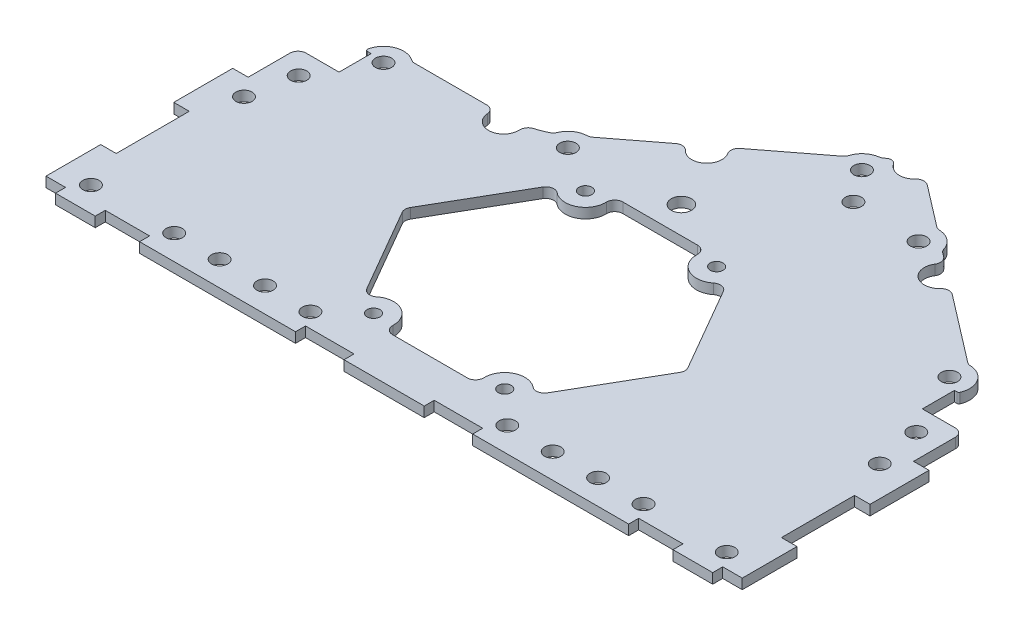
SolidWorks part; units mm, degrees
material "Alum Plate"
ref_plane "Front Plane" through (0, 0, 0) normal (0, 0, 1) x (1, 0, 0)
ref_plane "Top Plane" through (0, 0, 0) normal (0, 1, 0) x (1, 0, 0)
ref_plane "Right Plane" through (0, 0, 0) normal (1, 0, 0) x (0, 0, -1)
sketch "Top Layout" plane through (0, 0, 0) normal (0, 1, 0) x (1, 0, 0)
  line L0 (-114.046, -123.825) -> (-104.775, -123.825) construction
  line L1 (-104.775, -142.875) -> (-101.6, -142.875)
  line L2 (-104.775, -142.875) -> (-104.775, -104.775)
  line L3 (-104.775, -104.775) -> (-101.6, -104.775)
  line L4 (-101.6, -142.875) -> (-101.6, -104.775)
  line L5 (-104.775, -142.875) -> (-101.6, -104.775) construction
  line L6 (-104.775, -104.775) -> (-101.6, -142.875) construction
  line L7 (-19.05, -105.8164) -> (-101.6, -105.8164)
  line L8 (-19.05, -105.8164) -> (-19.05, -141.8336)
  line L9 (-19.05, -141.8336) -> (-101.6, -141.8336)
  line L10 (-101.6, -105.8164) -> (-101.6, -141.8336)
  line L11 (-19.05, -105.8164) -> (-101.6, -141.8336) construction
  line L12 (-19.05, -141.8336) -> (-101.6, -105.8164) construction
  line L13 (-133.096, -85.725) -> (-114.046, -85.725)
  line L14 (-133.096, -85.725) -> (-133.096, -161.925)
  line L15 (-133.096, -161.925) -> (-114.046, -161.925)
  line L16 (-114.046, -85.725) -> (-114.046, -161.925)
  line L17 (-133.096, -85.725) -> (-114.046, -161.925) construction
  line L18 (-133.096, -161.925) -> (-114.046, -85.725) construction
  line L19 (-104.775, -123.825) -> (0, -123.825) construction
  line L20 (0, -123.825) -> (0, 0) construction
  line L21 (-52.3528, -40.1717) -> (0, 0) construction
  line L22 (-70.6449, -16.3328) -> (-18.2922, 23.8388)
  line L23 (-34.0606, -64.0105) -> (18.2922, -23.8388)
  line L24 (-30.9251, 40.3023) -> (-122.2248, -29.7544)
  line L25 (-153.9748, -53.975) -> (-153.9748, -123.825)
  line L26 (-109.5248, -162.052) -> (109.5248, -162.052)
  line L27 (0, -162.052) -> (0, -123.825) construction
  line L28 (-109.5248, -162.052) -> (-109.5248, -20.0093) construction
  line L29 (-104.775, -142.875) -> (-104.775, -152.527)
  line L30 (-104.775, -152.527) -> (104.775, -152.527)
  line L31 (104.775, -104.775) -> (101.6, -104.775)
  line L32 (-144.4498, -73.025) -> (-109.5248, -73.025)
  line L33 (-144.4498, -73.025) -> (-144.4498, -123.825)
  line L34 (-144.4498, -123.825) -> (-109.5248, -123.825) construction
  line L35 (-109.5248, -73.025) -> (-109.5248, -162.052)
  line L36 (-144.4498, -73.025) -> (-109.5248, -123.825) construction
  line L37 (-144.4498, -123.825) -> (-109.5248, -73.025) construction
  line L38 (101.6, -142.875) -> (101.6, -104.775)
  line L39 (104.775, -142.875) -> (101.6, -142.875)
  line L40 (104.775, -142.875) -> (104.775, -104.775)
  line L41 (104.775, -142.875) -> (104.775, -152.527)
  line L42 (109.5248, -162.052) -> (109.5248, -20.0093) construction
  line L43 (30.9251, 40.3023) -> (122.2248, -29.7544)
  line L45 (19.05, -141.8336) -> (101.6, -141.8336)
  line L46 (101.6, -105.8164) -> (101.6, -141.8336)
  line L47 (19.05, -105.8164) -> (101.6, -105.8164)
  line L48 (19.05, -105.8164) -> (19.05, -141.8336)
  line L49 (133.096, -161.925) -> (114.046, -161.925)
  line L50 (114.046, -85.725) -> (114.046, -161.925)
  line L51 (133.096, -85.725) -> (114.046, -85.725)
  line L52 (133.096, -85.725) -> (133.096, -161.925)
  line L53 (144.4498, -123.825) -> (109.5248, -123.825) construction
  line L54 (109.5248, -73.025) -> (109.5248, -162.052)
  line L55 (144.4498, -73.025) -> (109.5248, -73.025)
  line L56 (144.4498, -73.025) -> (144.4498, -123.825)
  line L57 (-109.5248, -123.825) -> (-109.5248, -162.052) construction
  line L62 (-153.9748, -53.975) -> (-122.2248, -53.975)
  line L63 (-122.2248, -53.975) -> (-122.2248, -29.7544)
  line L64 (-144.4498, -123.825) -> (-153.9748, -123.825)
  line L65 (153.9748, -53.975) -> (153.9748, -123.825)
  line L66 (109.5248, -123.825) -> (109.5248, -162.052) construction
  line L67 (144.4498, -123.825) -> (153.9748, -123.825)
  line L68 (122.2248, -29.7544) -> (122.2248, -53.975)
  line L73 (-104.775, -104.775) -> (-104.775, -16.3647) construction
  line L74 (-95.25, -162.052) -> (-95.25, -9.0559) construction
  line L75 (-109.5248, -162.052) -> (-109.5248, -123.825) construction
  line L76 (109.5248, -162.052) -> (109.5248, -123.825) construction
  line L77 (122.2248, -53.975) -> (153.9748, -53.975)
  line L83 (104.775, -155.5496) -> (-104.775, -155.5496) construction
  line L88 (95.25, -162.052) -> (95.25, -9.0559) construction
  line L89 (104.775, -104.775) -> (104.775, -16.3647) construction
  line L92 (-104.775, -152.527) -> (-104.775, -162.052) construction
  line L93 (-14.605, -76.327) -> (14.605, -76.327)
  line L94 (-14.605, -76.327) -> (-14.605, -152.527)
  line L95 (-14.605, -152.527) -> (14.605, -152.527)
  line L96 (14.605, -76.327) -> (14.605, -152.527)
  line L97 (-14.605, -76.327) -> (14.605, -152.527) construction
  line L98 (-14.605, -152.527) -> (14.605, -76.327) construction
  line L99 (104.775, -152.527) -> (104.775, -162.052) construction
  line L100 (-19.05, -105.8164) -> (0, -105.8164) construction
  line L107 (0, -105.8164) -> (19.05, -105.8164) construction
  line L108 (104.775, -123.825) -> (114.046, -123.825) construction
  circle A0 centre (0, 0) radius 114.3
  circle A1 centre (0, 0) radius 6.35
  circle A2 centre (-52.3528, -40.1717) radius 17.8
  circle A3 centre (0, 0) radius 30.0482
  circle A4 centre (-52.3528, -40.1717) radius 30.0482
  arc A5 (-30.9251, 40.3023) -> (30.9251, 40.3023) centre (0, 0) cw
  point P2 (-103.1875, -123.825)
  point P7 (-60.325, -123.825)
  point P12 (-123.571, -123.825)
  point P30 (-126.9873, -98.425)
  point P35 (0, -114.427)
  point P53 (0, -152.527)
  dimension "D1" = 35.6
  dimension "D2" = 12.7
  dimension "D3" = 228.6
  dimension "D11" = 60.0964
  dimension "D12" = 50.8
  dimension "D14" = 52.5
  dimension "D4" = 3.175
  dimension "D5" = 19.05
  dimension "D6" = 76.2
  dimension "D7" = 82.55
  dimension "D8" = 38.1
  dimension "D9" = 104.775
  dimension "D10" = 18.0086
  dimension "D13" = 9.525
  dimension "D15" = 4.7498
  dimension "D16" = 9.525
  dimension "D17" = 9.652
  dimension "D18" = 50.8
  dimension "D19" = 12.446
  dimension "D20" = 65.9892
  dimension "D21" = 19.05
  dimension "D22" = 34.925
  dimension "D23" = 123.825
  dimension "D24" = 12.7
  dimension "D25" = 9.525
  dimension "D26" = 29.21
  dimension "D27" = 76.2
  dimension "D28" = 3.0226
sketch "Side Layout" plane through (0, 0, 0) normal (1, 0, 0) x (0, 0, -1)
  line L0 (0, -38.1) -> (0, 33.7344) construction
  line L1 (-114.3, -20.955) -> (114.3, -20.955)
  line L2 (-114.3, -20.955) -> (-114.3, -33.655)
  line L3 (-114.3, -33.655) -> (114.3, -33.655)
  line L4 (114.3, -20.955) -> (114.3, -33.655)
  line L5 (-114.3, -20.955) -> (114.3, -33.655) construction
  line L6 (-114.3, -33.655) -> (114.3, -20.955) construction
  line L7 (-9.525, -32.9406) -> (9.525, -32.9406)
  line L8 (-9.525, -32.9406) -> (-9.525, -38.1)
  line L9 (-9.525, -38.1) -> (9.525, -38.1)
  line L10 (9.525, -32.9406) -> (9.525, -38.1)
  line L11 (-9.525, -32.9406) -> (9.525, -38.1) construction
  line L12 (-9.525, -38.1) -> (9.525, -32.9406) construction
  line L13 (-11.9126, -29.3338) -> (11.9126, -29.3338)
  line L14 (-11.9126, -29.3338) -> (-11.9126, -32.9406)
  line L15 (-11.9126, -32.9406) -> (11.9126, -32.9406)
  line L16 (11.9126, -29.3338) -> (11.9126, -32.9406)
  line L17 (-11.9126, -29.3338) -> (11.9126, -32.9406) construction
  line L18 (-11.9126, -32.9406) -> (11.9126, -29.3338) construction
  line L19 (-6.35, -32.9406) -> (6.35, -32.9406)
  line L20 (-6.35, -32.9406) -> (-6.35, 33.7344)
  line L21 (-6.35, 33.7344) -> (6.35, 33.7344)
  line L22 (6.35, -32.9406) -> (6.35, 33.7344)
  line L23 (-6.35, -32.9406) -> (6.35, 33.7344) construction
  line L24 (-6.35, 33.7344) -> (6.35, -32.9406) construction
  line L25 (-162.052, 0) -> (-123.825, 0) construction
  line L26 (114.3, -33.655) -> (114.3, 0) construction
  line L27 (-142.875, 19.05) -> (-104.775, 19.05)
  line L28 (-40.1717, -9.525) -> (-40.1717, 5.4) construction
  line L29 (-142.875, 19.05) -> (-142.875, -19.05)
  line L30 (-142.875, -19.05) -> (-104.775, -19.05)
  line L31 (-104.775, 19.05) -> (-104.775, -19.05)
  line L32 (-142.875, 19.05) -> (-104.775, -19.05) construction
  line L33 (-142.875, -19.05) -> (-104.775, 19.05) construction
  line L34 (-130.175, -38.1) -> (-117.9516, -38.1) construction
  line L35 (-57.9717, -14.6) -> (-22.3717, -14.6)
  line L36 (-30.0482, -2.794) -> (30.0482, -2.794)
  line L37 (-30.0482, -2.794) -> (-30.0482, -20.955)
  line L38 (-30.0482, -20.955) -> (30.0482, -20.955)
  line L39 (30.0482, -2.794) -> (30.0482, -20.955)
  line L40 (-30.0482, -2.794) -> (30.0482, -20.955) construction
  line L41 (-30.0482, -20.955) -> (30.0482, -2.794) construction
  line L42 (-30.0482, -2.794) -> (-30.0482, 0) construction
  line L43 (-123.825, 0) -> (0, 0) construction
  line L44 (-57.9717, -14.6) -> (-57.9717, 25.4)
  line L45 (-57.9717, 25.4) -> (-22.3717, 25.4)
  line L46 (-22.3717, -14.6) -> (-22.3717, 25.4)
  line L47 (-19.05, 0) -> (19.05, 0)
  line L48 (-19.05, 0) -> (-19.05, -1.9812)
  line L49 (-19.05, -1.9812) -> (19.05, -1.9812)
  line L50 (19.05, 0) -> (19.05, -1.9812)
  line L51 (-19.05, 0) -> (19.05, -1.9812) construction
  line L52 (-19.05, -1.9812) -> (19.05, 0) construction
  line L53 (-70.2199, -3.175) -> (-10.1235, -3.175)
  line L54 (-70.2199, -3.175) -> (-70.2199, -15.875)
  line L55 (-70.2199, -15.875) -> (-10.1235, -15.875)
  line L56 (-10.1235, -3.175) -> (-10.1235, -15.875)
  line L57 (-70.2199, -3.175) -> (-10.1235, -15.875) construction
  line L58 (-70.2199, -15.875) -> (-10.1235, -3.175) construction
  line L59 (-40.1717, -9.525) -> (-40.1717, 0) construction
  line L60 (-57.9717, -14.6) -> (-22.3717, 25.4) construction
  line L61 (-57.9717, 25.4) -> (-22.3717, -14.6) construction
  line L62 (-22.3717, 0) -> (-57.9717, 0) construction
  line L63 (-137.8162, 0) -> (-123.825, -13.9912) construction
  line L64 (-139.065, 15.24) -> (-108.585, 15.24) construction
  line L65 (-139.065, 15.24) -> (-139.065, -15.24) construction
  line L66 (-139.065, -15.24) -> (-108.585, -15.24) construction
  line L67 (-108.585, 15.24) -> (-108.585, -15.24) construction
  line L68 (-139.065, 15.24) -> (-108.585, -15.24) construction
  line L69 (-139.065, -15.24) -> (-108.585, 15.24) construction
  line L70 (-137.8162, 0) -> (-123.825, 13.9912) construction
  line L71 (-123.825, -13.9912) -> (-109.8338, 0) construction
  line L72 (-123.825, 13.9912) -> (-109.8338, 0) construction
  line L73 (-137.8162, 0) -> (-109.8338, 0) construction
  line L74 (-123.825, -13.9912) -> (-123.825, 13.9912) construction
  line L75 (-6.35, 17.8594) -> (6.35, 17.8594)
  line L76 (114.3, 0) -> (-114.3, 0) construction
  line L77 (-22.3717, 19.05) -> (-6.35, 19.05) construction
  line L78 (-123.825, 38.1) -> (-97.9206, 38.1) construction
  line L79 (-19.05, -3.5814) -> (19.05, -3.5814)
  line L80 (-19.05, -3.5814) -> (-19.05, -1.9812)
  line L81 (-19.05, -1.9812) -> (19.05, -1.9812)
  line L82 (19.05, -3.5814) -> (19.05, -1.9812)
  line L83 (-19.05, -3.5814) -> (19.05, -1.9812) construction
  line L84 (-19.05, -1.9812) -> (19.05, -3.5814) construction
  line L85 (-8.7376, -16.7608) -> (8.7376, -16.7608)
  line L86 (-8.7376, -16.7608) -> (-8.7376, -29.3338)
  line L87 (-8.7376, -29.3338) -> (8.7376, -29.3338)
  line L88 (8.7376, -16.7608) -> (8.7376, -29.3338)
  line L89 (-8.7376, -16.7608) -> (8.7376, -29.3338) construction
  line L90 (-8.7376, -29.3338) -> (8.7376, -16.7608) construction
  line L91 (-8.7376, -3.5814) -> (8.7376, -3.5814)
  line L92 (-8.7376, -3.5814) -> (-8.7376, -16.1544)
  line L93 (-8.7376, -16.1544) -> (8.7376, -16.1544)
  line L94 (8.7376, -3.5814) -> (8.7376, -16.1544)
  line L95 (-8.7376, -3.5814) -> (8.7376, -16.1544) construction
  line L96 (-8.7376, -16.1544) -> (8.7376, -3.5814) construction
  circle A0 centre (-123.825, 0) radius 18.0086
  circle A1 centre (-123.825, 0) radius 38.1
  circle A2 centre (-139.065, 15.24) radius 1.905
  circle A3 centre (-108.585, 15.24) radius 1.905
  circle A4 centre (-108.585, -15.24) radius 1.905
  circle A5 centre (-139.065, -15.24) radius 1.905
  circle A6 centre (-137.8162, 0) radius 1.6002
  circle A7 centre (-123.825, 13.9912) radius 1.6002
  circle A8 centre (-109.8338, 0) radius 1.6002
  circle A9 centre (-123.825, -13.9912) radius 1.6002
  point P0 (0, -27.305)
  point P6 (0, -31.1372)
  point P7 (0, -35.5203)
  point P21 (0, 0.3969)
  point P32 (0, -11.8745)
  point P43 (0, -0.9906)
  point P55 (-40.1717, -9.525)
  point P72 (-40.1717, 5.4)
  point P88 (0, -23.0473)
  point P93 (0, -2.7813)
  point P102 (0, -9.8679)
  dimension "D17" = 3.81
  dimension "D18" = 3.2004
  dimension "D1" = 12.7
  dimension "D2" = 5.1594
  dimension "D3" = 19.05
  dimension "D4" = 3.6068
  dimension "D5" = 23.8252
  dimension "D6" = 12.7
  dimension "D7" = 18.161
  dimension "D8" = 1.9812
  dimension "D9" = 12.7
  dimension "D10" = 40
  dimension "D11" = 25.4
  dimension "D12" = 50.8
  dimension "D13" = 41.275
  dimension "D14" = 30.48
  dimension "D15" = 4.445
  dimension "D16" = 19.7866
  dimension "D19" = 15.875
  dimension "D20" = 6.35
  dimension "D21" = 38.1
  dimension "D22" = 1.6002
  dimension "D23" = 38.1
  dimension "D24" = 17.4752
  dimension "D25" = 12.573
ref_plane "Plane1" through (0, 25.4, 0) normal (0, 1, 0) x (1, 0, 0)
sketch "Sketch3" plane through (0, 25.4, 0) normal (0, 1, 0) x (1, 0, 0)
  line L0 (-104.775, -36.3747) -> (-30.9251, 20.2924)
  line L1 (-104.775, -104.775) -> (-104.775, -16.3647) construction
  line L2 (0, -200130.175) -> (0, 199882.0484) construction
  line L3 (-30.9251, 40.3023) -> (-122.2248, -29.7544) construction
  line L5 (-104.775, -36.3747) -> (-104.775, -77.6497)
  line L6 (-92.075, -77.6497) -> (-104.775, -77.6497)
  line L7 (30.9251, 20.2924) -> (104.775, -36.3747)
  line L8 (104.775, -77.6497) -> (92.075, -77.6497)
  line L9 (104.775, -36.3747) -> (104.775, -77.6497)
  line L11 (104.775, -104.775) -> (104.775, -16.3647) construction
  line L12 (30.9251, 40.3023) -> (122.2248, -29.7544) construction
  line L13 (92.075, -74.6536) -> (24.1423, -22.5271)
  line L14 (-32.2514, -66.3682) -> (20.1013, -26.1965)
  line L15 (-30.9251, 20.2924) -> (0, 44.022)
  line L16 (0, 44.022) -> (30.9251, 20.2924)
  line L17 (-92.075, -77.6497) -> (-92.075, -73.1917)
  line L19 (-92.075, -73.1917) -> (-52.3528, -73.1917)
  line L20 (92.075, -74.6536) -> (92.075, -77.6497)
  circle A0 centre (-52.3528, -40.1717) radius 17.8 construction
  circle A1 centre (-52.3528, -40.1717) radius 17.8
  circle A2 centre (0, 0) radius 6.35
  circle A3 centre (0, 0) radius 6.35 construction
  arc A4 (-52.3528, -73.1917) -> (-32.2514, -66.3682) centre (-52.3528, -40.1717) ccw
  arc A5 (20.1013, -26.1965) -> (24.1423, -22.5271) centre (0, 0) ccw
  arc A6 (30.9251, 20.2924) -> (-30.9251, 20.2924) centre (0, -20.01) ccw construction
  point P28 (0, 44.022)
  dimension "D1" = 33.02
  dimension "D5" = 50.8
  dimension "D2" = 41.275
  dimension "D3" = 34.925
  dimension "D4" = 12.7
  dimension "D6" = 38.1
ref_plane "Plane3" through (-104.775, 0, 0) normal (-1, 0, 0) x (0, 0, 1)
sketch "Sketch6" plane through (-104.775, 0, 0) normal (-1, 0, 0) x (0, 0, 1)
  line L0 (162.052, -25.4) -> (162.052, 25.4)
  line L1 (162.052, 25.4) -> (77.6497, 25.4)
  line L2 (36.3747, 25.4) -> (77.6497, 25.4) construction
  line L3 (147.7645, 11.1125) -> (162.052, 11.1125) construction
  line L4 (162.052, 0) -> (71.2997, 0) construction
  line L5 (77.6497, 25.4) -> (77.6497, 19.05)
  line L6 (77.6497, 19.05) -> (36.3747, 19.05)
  line L7 (36.3747, 19.05) -> (36.3747, 6.35)
  line L8 (36.3747, 6.35) -> (71.2997, 6.35)
  line L10 (99.6315, -3.175) -> (99.6315, 11.1125) construction
  line L11 (71.2997, -25.4) -> (162.052, -25.4)
  line L13 (71.2997, 6.35) -> (71.2997, -25.4)
  line L14 (152.527, -25.4) -> (152.527, 25.4) construction
  line L15 (99.6315, 11.1125) -> (99.6315, 25.4) construction
  line L16 (147.7645, 11.1125) -> (147.7645, 25.4) construction
  line L17 (94.869, -7.9375) -> (104.394, -7.9375) construction
  line L18 (94.869, -7.9375) -> (94.869, 25.4) construction
  line L19 (94.869, 25.4) -> (104.394, 25.4) construction
  line L20 (104.394, -7.9375) -> (104.394, 25.4) construction
  line L21 (94.869, -7.9375) -> (104.394, 25.4) construction
  line L22 (94.869, 25.4) -> (104.394, -7.9375) construction
  line L23 (147.7645, 11.1125) -> (147.7645, -3.175) construction
  line L24 (104.394, -7.9375) -> (123.825, -7.9375) construction
  line L25 (143.002, -7.9375) -> (152.527, -7.9375) construction
  line L26 (143.002, -7.9375) -> (143.002, 25.4) construction
  line L27 (143.002, 25.4) -> (152.527, 25.4) construction
  line L28 (152.527, -7.9375) -> (152.527, 25.4) construction
  line L29 (143.002, -7.9375) -> (152.527, 25.4) construction
  line L30 (143.002, 25.4) -> (152.527, -7.9375) construction
  line L31 (123.825, -7.9375) -> (152.527, -7.9375) construction
  line L32 (104.775, 19.05) -> (104.775, -19.05) construction
  line L34 (155.702, -25.4) -> (155.702, 25.4) construction
  circle A0 centre (109.8338, 0) radius 1.6002 construction
  circle A1 centre (123.825, 13.9912) radius 1.6002 construction
  circle A2 centre (137.8162, 0) radius 1.6002 construction
  circle A3 centre (123.825, -13.9912) radius 1.6002 construction
  circle A4 centre (109.8338, 0) radius 1.6002 construction
  circle A5 centre (123.825, 13.9912) radius 1.6002 construction
  circle A6 centre (137.8162, 0) radius 1.6002 construction
  circle A7 centre (123.825, -13.9912) radius 1.6002 construction
  circle A8 centre (123.825, 0) radius 18.0086 construction
  circle A9 centre (123.825, 0) radius 18.0086 construction
  circle A10 centre (123.825, 0) radius 9.525
  circle A11 centre (108.585, -15.24) radius 1.905 construction
  circle A12 centre (108.585, 15.24) radius 1.905 construction
  circle A13 centre (139.065, 15.24) radius 1.905 construction
  circle A14 centre (139.065, -15.24) radius 1.905 construction
  circle A15 centre (108.585, -15.24) radius 1.905
  circle A16 centre (108.585, 15.24) radius 1.905
  circle A17 centre (139.065, 15.24) radius 1.905
  circle A18 centre (139.065, -15.24) radius 1.905
  circle A19 centre (147.7645, 11.1125) radius 2.5527
  circle A26 centre (99.6315, 11.1125) radius 2.5527
  circle A27 centre (99.6315, -3.175) radius 2.5527
  circle A28 centre (147.7645, -3.175) radius 2.5527
  point P29 (0, 0)
  point P55 (99.6315, 8.7312)
  point P61 (147.7645, 8.7312)
  dimension "D4" = 19.05
  dimension "D7" = 5.1054
  dimension "D1" = 6.35
  dimension "D2" = 12.7
  dimension "D3" = 25.4
  dimension "D5" = 6.35
  dimension "D6" = 3.175
  dimension "D8" = 0.381
  dimension "D9" = 14.2875
  dimension "D10" = 9.525
  dimension "D12" = 33.3375
ref_plane "Plane4" through (0, 19.05, 0) normal (0, 1, 0) x (1, 0, 0)
sketch "Sketch12" plane through (0, 19.05, 0) normal (0, 1, 0) x (1, 0, 0)
  line L0 (-104.775, -77.6497) -> (-104.775, -36.3747)
  line L1 (-104.775, -36.3747) -> (-92.075, -36.3747)
  line L3 (-92.075, -36.3747) -> (-92.075, -77.6497)
  line L5 (-92.075, -77.6497) -> (-104.775, -77.6497)
  line L6 (-98.425, -77.6497) -> (-98.425, -63.3622) construction
  line L7 (-98.425, -63.3622) -> (-98.425, -50.6622) construction
  line L8 (-98.425, -50.6622) -> (-98.425, -36.3747) construction
  line L10 (-98.425, -36.3747) -> (-104.775, -36.3747) construction
  circle A0 centre (-98.425, -63.3622) radius 2.5527
  circle A1 centre (-98.425, -50.6622) radius 2.5527
  dimension "D2" = 5.1054
  dimension "D1" = 12.7
  dimension "D3" = 12.7
sketch "Sketch25" plane through (0, 25.4, 0) normal (0, 1, 0) x (1, 0, 0)
  line L0 (-104.775, -152.527) -> (104.775, -152.527)
  line L1 (-104.775, -152.527) -> (104.775, -152.527) construction
  line L2 (104.775, -152.527) -> (104.775, -162.052)
  line L3 (104.775, -162.052) -> (-104.775, -162.052)
  line L4 (-104.775, -162.052) -> (-104.775, -152.527)
ref_plane "Plane5" through (0, 0, 152.527) normal (0, 0, 1) x (1, 0, 0)
sketch "Sketch41" plane through (0, 0, 152.527) normal (0, 0, 1) x (1, 0, 0)
  line L0 (-104.775, -7.9375) -> (-104.775, 25.4) construction
  line L1 (-104.775, -7.9375) -> (-104.775, 12.7)
  line L2 (-104.775, -7.9375) -> (104.775, -7.9375)
  line L3 (104.775, -7.9375) -> (104.775, 12.7)
  line L4 (104.775, 25.4) -> (-104.775, 25.4)
  line L5 (0, -7.9375) -> (0, 25.4) construction
  line L6 (-104.775, 3.9624) -> (-100.0125, 3.9624) construction
  line L7 (-100.0125, 3.9624) -> (-100.0125, 25.4) construction
  line L8 (104.775, 3.9624) -> (100.0125, 3.9624) construction
  line L9 (100.0125, 3.9624) -> (100.0125, 25.4) construction
  line L10 (19.05, 20.6375) -> (23.8252, 20.6375) construction
  line L11 (19.05, 15.875) -> (78.5876, 15.875) construction
  line L12 (19.05, 15.875) -> (19.05, 25.4) construction
  line L13 (19.05, 25.4) -> (78.5876, 25.4) construction
  line L14 (78.5876, 15.875) -> (78.5876, 25.4) construction
  line L15 (19.05, 15.875) -> (78.5876, 25.4) construction
  line L16 (19.05, 25.4) -> (78.5876, 15.875) construction
  line L17 (23.8252, 20.6375) -> (38.1127, 20.6375) construction
  line L18 (38.1127, 20.6375) -> (52.4002, 20.6375) construction
  line L19 (52.4002, 20.6375) -> (66.6877, 20.6375) construction
  line L20 (-104.775, 25.4) -> (-112.395, 25.4)
  line L21 (-112.395, 25.4) -> (-112.395, 3.175)
  line L22 (-112.395, 3.175) -> (-109.5248, 3.175)
  line L23 (-109.5248, 3.175) -> (-109.5248, 12.7)
  line L24 (-109.5248, 12.7) -> (-104.775, 12.7)
  line L25 (-104.775, 12.7) -> (-104.775, 25.4) construction
  line L26 (104.775, 25.4) -> (112.395, 25.4)
  line L27 (112.395, 25.4) -> (112.395, 3.175)
  line L28 (112.395, 3.175) -> (109.5248, 3.175)
  line L29 (109.5248, 3.175) -> (109.5248, 12.7)
  line L30 (109.5248, 12.7) -> (104.775, 12.7)
  line L31 (104.775, 12.7) -> (104.775, 25.4) construction
  line L32 (-100.0125, 3.9624) -> (-87.3125, 3.9624) construction
  line L33 (-63.5, -1.5875) -> (0, -1.5875) construction
  line L34 (0, -1.5875) -> (63.5, -1.5875) construction
  line L35 (63.5, -1.5875) -> (63.5, -7.9375) construction
  circle A0 centre (-100.0125, 3.9624) radius 2.5527
  circle A1 centre (100.0125, 3.9624) radius 2.5527
  circle A2 centre (23.8252, 20.6375) radius 2.5527
  circle A3 centre (38.1127, 20.6375) radius 2.5527
  circle A4 centre (52.4002, 20.6375) radius 2.5527
  circle A5 centre (66.6877, 20.6375) radius 2.5527
  circle A6 centre (-66.6877, 20.6375) radius 2.5527
  circle A7 centre (-52.4002, 20.6375) radius 2.5527
  circle A8 centre (-38.1127, 20.6375) radius 2.5527
  circle A9 centre (-23.8252, 20.6375) radius 2.5527
  circle A10 centre (-87.3125, 3.9624) radius 2.5527
  circle A11 centre (87.3125, 3.9624) radius 2.5527
  circle A12 centre (-63.5, -1.5875) radius 2.5527
  circle A13 centre (63.5, -1.5875) radius 2.5527
  point P14 (48.8188, 20.6375)
  dimension "D3" = 5.1054
  dimension "D7" = 5.1054
  dimension "D1" = 21.4376
  dimension "D2" = 4.7625
  dimension "D4" = 9.525
  dimension "D5" = 59.5376
  dimension "D6" = 4.7752
  dimension "D8" = 14.2875
  dimension "D9" = 7.62
  dimension "D10" = 4.7498
  dimension "D11" = 12.7
  dimension "D12" = 9.525
  dimension "D13" = 19.05
  dimension "D14" = 12.7
  dimension "D15" = 6.35
  dimension "D16" = 63.5
sketch "Sketch44" plane through (0, 25.4, 0) normal (0, 1, 0) x (1, 0, 0)
  line L0 (73.8315, -147.7645) -> (73.8315, -152.527) construction
  line L1 (92.075, -74.6536) -> (92.075, -77.6497) construction
  line L2 (-92.075, -77.6497) -> (-92.075, -73.1917) construction
  line L3 (0, -123.825) -> (0, 0) construction
  line L4 (-92.075, -73.1917) -> (-52.3528, -73.1917) construction
  line L5 (-104.775, -104.775) -> (-104.775, -16.3647) construction
  line L6 (-32.2514, -66.3682) -> (20.1013, -26.1965) construction
  line L21 (-104.775, -68.1247) -> (-104.775, -152.527)
  line L22 (-104.775, -152.527) -> (104.775, -152.527)
  line L23 (104.775, -152.527) -> (104.775, -68.1247)
  line L34 (-104.775, -99.6315) -> (-100.0125, -99.6315) construction
  line L35 (-104.775, -147.7645) -> (-100.0125, -147.7645) construction
  line L36 (0, -152.527) -> (0, -35.6178) construction
  line L38 (30.969, -147.7645) -> (45.2565, -147.7645) construction
  line L39 (45.2565, -147.7645) -> (59.544, -147.7645) construction
  line L40 (59.544, -147.7645) -> (73.8315, -147.7645) construction
  line L41 (23.8252, -152.527) -> (30.969, -152.527) construction
  line L42 (104.775, -152.527) -> (-104.775, -152.527) construction
  line L43 (30.969, -152.527) -> (38.1127, -152.527) construction
  line L44 (30.969, -152.527) -> (30.969, -147.7645) construction
  line L45 (-92.075, -77.6497) -> (-104.775, -77.6497) construction
  line L48 (-35.1507, -62.5899) -> (-8.9743, -42.504) construction
  line L49 (-8.9743, -42.504) -> (17.2021, -22.4182) construction
  line L50 (45.5313, -32.9364) -> (87.3125, -64.9962) construction
  line L51 (92.075, -74.6536) -> (24.1423, -22.5271) construction
  line L52 (104.775, -77.6497) -> (92.075, -77.6497) construction
  line L79 (-104.775, -68.1247) -> (-92.075, -68.1247)
  line L80 (-92.075, -68.1247) -> (-92.075, -63.6667)
  line L85 (21.8118, -8.7328) -> (92.075, -62.6476)
  line L86 (-38.0499, -58.8115) -> (14.3028, -18.6398)
  line L87 (-92.075, -63.6667) -> (-52.3528, -63.6667)
  line L88 (92.075, -62.6476) -> (92.075, -68.1247)
  line L89 (92.075, -68.1247) -> (104.775, -68.1247)
  circle A0 centre (-73.8315, -147.7645) radius 2.5527
  circle A1 centre (-59.544, -147.7645) radius 2.5527
  circle A2 centre (-45.2565, -147.7645) radius 2.5527
  circle A3 centre (-30.969, -147.7645) radius 2.5527
  circle A17 centre (-100.0125, -99.6315) radius 2.5527
  circle A18 centre (-100.0125, -147.7645) radius 2.5527
  circle A19 centre (100.0125, -147.7645) radius 2.5527
  circle A20 centre (100.0125, -99.6315) radius 2.5527
  circle A21 centre (30.969, -147.7645) radius 2.5527
  circle A22 centre (45.2565, -147.7645) radius 2.5527
  circle A23 centre (59.544, -147.7645) radius 2.5527
  circle A24 centre (73.8315, -147.7645) radius 2.5527
  circle A25 centre (-87.3125, -68.4292) radius 4.7625 construction
  circle A26 centre (-35.1507, -62.5899) radius 4.7625 construction
  circle A27 centre (-8.9743, -42.504) radius 4.7625 construction
  circle A28 centre (17.2021, -22.4182) radius 4.7625 construction
  circle A29 centre (45.5313, -32.9364) radius 4.7625 construction
  circle A30 centre (87.3125, -64.9962) radius 4.7625 construction
  circle A32 centre (-87.3125, -68.4292) radius 2.5527
  circle A33 centre (-35.1507, -62.5899) radius 2.5527
  circle A34 centre (-8.9743, -42.504) radius 2.5527 construction
  circle A35 centre (17.2021, -22.4182) radius 2.5527
  circle A36 centre (45.5313, -32.9364) radius 2.5527
  circle A37 centre (87.3125, -64.9962) radius 2.5527
  circle A38 centre (-97.155, -85.2697) radius 7.62 construction
  circle A39 centre (97.155, -85.2697) radius 7.62 construction
  circle A40 centre (24.5121, -32.4156) radius 7.62 construction
  arc A41 (20.1013, -26.1965) -> (24.1423, -22.5271) centre (0, 0) ccw construction
  circle A42 centre (-97.155, -85.2697) radius 2.5527
  circle A43 centre (24.5121, -32.4156) radius 2.5527
  circle A44 centre (97.155, -85.2697) radius 2.5527
  arc A56 (14.3028, -18.6398) -> (21.8118, -8.7328) centre (0, 0) ccw
  arc A57 (-52.3528, -63.6667) -> (-38.0499, -58.8115) centre (-52.3528, -40.1717) ccw
  point P4 (-104.775, -152.527)
  dimension "D2" = 5.1054
  dimension "D7" = 5.1054
  dimension "D8" = 15.24
  dimension "D3" = 9.525
  dimension "D9" = 9.525
  dimension "D4" = 4.7625
  dimension "D5" = 14.2875
  dimension "D6" = 9.525
  dimension "D1" = 4.7625
  dimension "D10" = 52.664
extrude "Top Plate Extrude-----------" add sketch "Sketch44" along normal blind 3.175
sketch "Sketch82" plane through (0, 28.575, 0) normal (0, 1, 0) x (1, 0, 0)
  line L0 (-52.3528, -63.6667) -> (-92.075, -63.6667) construction
  line L1 (-52.3528, -65.5717) -> (-52.3528, -63.6667) construction
  line L2 (-12.4467, -41.5667) -> (-13.6064, -40.0553) construction
  line L3 (14.3028, -18.6398) -> (-38.0499, -58.8115) construction
  line L4 (24.5175, -13.2101) -> (25.6772, -11.6988) construction
  line L5 (92.075, -62.6476) -> (21.8118, -8.7328) construction
  line L6 (58.2962, -39.1295) -> (59.4559, -37.6181) construction
  line L7 (21.4643, -9.5551) -> (21.8118, -8.7328)
  line L8 (21.8118, -8.7328) -> (22.2143, -9.0416)
  circle A0 centre (-52.3528, -65.5717) radius 4.7625
  circle A1 centre (-12.4467, -41.5667) radius 4.7625
  arc A2 (21.4643, -9.5551) -> (22.2143, -9.0416) centre (24.5175, -13.2101) ccw
  circle A3 centre (58.2962, -39.1295) radius 4.7625
  arc A4 (14.3028, -18.6398) -> (21.8118, -8.7328) centre (0, 0) ccw construction
  dimension "D1" = 9.525
  dimension "D2" = 1.905
  dimension "D3" = 30.8104
  dimension "D4" = 83.6926
  dimension "D5" = 41.1154
extrude "Cut-Extrude38" cut sketch "Sketch82" against normal up to surface (3.175 mm away) up to face at (-4.435, 25.4, 71.2837)
sketch "Sketch72" plane through (0, 25.4, 0) normal (0, 1, 0) x (1, 0, 0)
  line L0 (-104.775, -68.1247) -> (-104.775, -152.527) construction
  line L1 (-104.775, -152.527) -> (-109.5248, -152.527)
  line L2 (-104.775, -152.527) -> (-104.775, -135.0645)
  line L3 (-104.775, -135.0645) -> (-109.5248, -135.0645)
  line L4 (-109.5248, -152.527) -> (-109.5248, -135.0645)
  line L5 (-104.775, -152.527) -> (-109.5248, -135.0645) construction
  line L6 (-104.775, -135.0645) -> (-109.5248, -152.527) construction
  line L7 (-104.775, -152.527) -> (104.775, -152.527) construction
  line L8 (-77.0065, -152.527) -> (-73.8315, -147.7645) construction
  line L9 (-77.0065, -152.527) -> (-27.794, -152.527)
  line L10 (-77.0065, -152.527) -> (-77.0065, -155.5496)
  line L11 (-77.0065, -155.5496) -> (-27.794, -155.5496)
  line L12 (-27.794, -152.527) -> (-27.794, -155.5496)
  line L13 (-77.0065, -152.527) -> (-27.794, -155.5496) construction
  line L14 (-77.0065, -155.5496) -> (-27.794, -152.527) construction
  line L15 (-27.794, -152.527) -> (-30.969, -147.7645) construction
  line L16 (-77.0065, -152.527) -> (-77.0065, -147.7645) construction
  line L18 (-104.775, -93.5247) -> (-109.5248, -93.5247)
  line L19 (-104.775, -93.5247) -> (-104.775, -112.3315)
  line L20 (-104.775, -112.3315) -> (-109.5248, -112.3315)
  line L21 (-109.5248, -93.5247) -> (-109.5248, -112.3315)
  line L22 (-104.775, -93.5247) -> (-109.5248, -112.3315) construction
  line L23 (-104.775, -112.3315) -> (-109.5248, -93.5247) construction
  line L24 (0, -152.527) -> (-12.7, -152.527)
  line L25 (0, -152.527) -> (0, -155.5496)
  line L26 (0, -155.5496) -> (-12.7, -155.5496)
  line L27 (-12.7, -152.527) -> (-12.7, -155.5496)
  line L28 (0, -152.527) -> (-12.7, -155.5496) construction
  line L29 (0, -155.5496) -> (-12.7, -152.527) construction
  line L30 (-104.775, -68.1247) -> (-109.5248, -68.1247)
  line L31 (-104.775, -68.1247) -> (-104.775, -77.6497)
  line L32 (-104.775, -77.6497) -> (-109.5248, -77.6497)
  line L33 (-109.5248, -68.1247) -> (-109.5248, -77.6497)
  line L34 (-104.775, -68.1247) -> (-109.5248, -77.6497) construction
  line L35 (-104.775, -77.6497) -> (-109.5248, -68.1247) construction
  line L38 (-103.505, -155.5496) -> (-90.805, -155.5496)
  line L39 (-90.805, -152.527) -> (-90.805, -155.5496)
  line L40 (-103.505, -155.5496) -> (-103.505, -152.527)
  line L41 (-103.505, -155.5496) -> (-90.805, -152.527) construction
  line L42 (-103.505, -152.527) -> (-90.805, -152.527)
  line L43 (-77.0065, -147.7645) -> (-73.8315, -147.7645) construction
  line L44 (-103.505, -152.527) -> (-101.5221, -149.823) construction
  circle A0 centre (-100.0125, -147.7645) radius 2.5527 construction
  circle A1 centre (-73.8315, -147.7645) radius 2.5527 construction
  circle A2 centre (-30.969, -147.7645) radius 2.5527 construction
  point P4 (-107.1499, -143.7958)
  point P5 (-100.0125, -147.7645)
  point P16 (-52.4002, -154.0383)
  point P18 (-97.155, -154.0383)
  point P25 (-107.1499, -102.9281)
  point P34 (-6.35, -154.0383)
  point P39 (-107.1499, -72.8872)
  dimension "D1" = 4.7498
  dimension "D2" = 12.7
  dimension "D3" = 12.7
  dimension "D4" = 12.7
  dimension "D5" = 9.525
  dimension "D6" = 15.875
  dimension "D7" = 12.7
  dimension "D8" = 3.175
  dimension "D9" = 1.27
  dimension "D10" = 3.0226
extrude "Boss-Extrude27" add sketch "Sketch72" along normal through all
mirror "Mirror22" about plane through (0, 0, 0) normal (1, 0, 0) of "Boss-Extrude27"
sketch "Sketch86" plane through (0, 28.575, 0) normal (0, 1, 0) x (1, 0, 0)
  circle A0 centre (87.3125, -64.9962) radius 6.35
  circle A3 centre (17.2021, -22.4182) radius 6.35
  circle A4 centre (45.5313, -32.9364) radius 6.35
  circle A5 centre (-35.1507, -62.5899) radius 6.35
  circle A6 centre (-87.3125, -68.4292) radius 6.35
  circle A7 centre (87.3125, -64.9962) radius 2.5527 construction
  circle A8 centre (45.5313, -32.9364) radius 2.5527 construction
  circle A9 centre (17.2021, -22.4182) radius 2.5527 construction
  circle A10 centre (-35.1507, -62.5899) radius 2.5527 construction
  circle A11 centre (-87.3125, -68.4292) radius 2.5527 construction
  circle A12 centre (87.3125, -64.9962) radius 2.5527
  circle A13 centre (45.5313, -32.9364) radius 2.5527
  circle A14 centre (17.2021, -22.4182) radius 2.5527
  circle A15 centre (-35.1507, -62.5899) radius 2.5527
  circle A16 centre (-87.3125, -68.4292) radius 2.5527
  dimension "D1" = 12.7
extrude "Boss-Extrude31" add sketch "Sketch86" against normal through all
ref_plane "Plane8" through (0, 28.829, 0) normal (0, 1, 0) x (1, 0, 0)
sketch "Sketch87" plane through (0, 28.829, 0) normal (0, 1, 0) x (1, 0, 0)
  line L0 (0, -123.825) -> (0, 0) construction
  line L1 (-25.4, -66.802) -> (25.4, -66.802)
  line L2 (-25.4, -66.802) -> (-25.4, -143.002) construction
  line L3 (-25.4, -143.002) -> (25.4, -143.002)
  line L4 (25.4, -66.802) -> (25.4, -143.002) construction
  line L5 (-25.4, -66.802) -> (25.4, -143.002) construction
  line L6 (-25.4, -143.002) -> (25.4, -66.802) construction
  line L7 (-104.775, -152.527) -> (104.775, -152.527) construction
  line L8 (-25.4, -71.5645) -> (-20.6375, -71.5645) construction
  line L9 (-20.6375, -71.5645) -> (-20.6375, -66.802) construction
  line L10 (20.6375, -66.802) -> (20.6375, -71.5645) construction
  line L11 (20.6375, -71.5645) -> (25.4, -71.5645) construction
  line L12 (20.6375, -143.002) -> (20.6375, -138.2395) construction
  line L13 (20.6375, -138.2395) -> (25.4, -138.2395) construction
  line L14 (-20.6375, -143.002) -> (-20.6375, -138.2395) construction
  line L15 (-20.6375, -138.2395) -> (-25.4, -138.2395) construction
  line L16 (-25.4, -143.002) -> (-47.397, -104.902)
  line L17 (-47.397, -104.902) -> (-25.4, -66.802)
  line L18 (25.4, -66.802) -> (47.397, -104.902)
  line L19 (47.397, -104.902) -> (25.4, -143.002)
  circle A0 centre (-20.6375, -71.5645) radius 2.5527
  circle A1 centre (20.6375, -71.5645) radius 2.5527
  circle A3 centre (-20.6375, -138.2395) radius 2.5527
  circle A4 centre (20.6375, -138.2395) radius 2.5527
  point P0 (0, -104.902)
  dimension "D5" = 5.1054
  dimension "D1" = 50.8
  dimension "D2" = 9.525
  dimension "D3" = 76.2
  dimension "D4" = 4.7625
  dimension "D6" = 120
sketch "Sketch111" plane through (0, 28.575, 0) normal (0, 1, 0) x (1, 0, 0)
  line L0 (-109.5248, -77.6497) -> (-104.775, -77.6497) construction
  line L1 (-109.5248, -67.8707) -> (-91.7575, -67.8707)
  line L2 (-109.5248, -67.8707) -> (-109.5248, -77.9672)
  line L3 (-109.5248, -77.9672) -> (-91.7575, -77.9672)
  line L4 (-91.7575, -67.8707) -> (-91.7575, -77.9672)
  line L5 (-109.5248, -67.8707) -> (-91.7575, -77.9672) construction
  line L6 (-109.5248, -77.9672) -> (-91.7575, -67.8707) construction
  line L7 (109.5248, -67.8707) -> (91.7575, -67.8707)
  line L8 (109.5248, -67.8707) -> (109.5248, -77.9672)
  line L9 (109.5248, -77.9672) -> (91.7575, -77.9672)
  line L10 (91.7575, -67.8707) -> (91.7575, -77.9672)
  line L11 (109.5248, -67.8707) -> (91.7575, -77.9672) construction
  line L12 (109.5248, -77.9672) -> (91.7575, -67.8707) construction
  line L13 (-93.6552, -68.1247) -> (-109.5248, -68.1247) construction
  line L14 (-109.5248, -68.1247) -> (-109.5248, -77.6497) construction
  line L15 (109.5248, -68.1247) -> (109.5248, -77.6497) construction
  line L16 (-104.775, -104.775) -> (-104.775, -16.3647) construction
  point P4 (-100.6411, -72.9189)
  point P10 (100.6411, -72.9189)
  dimension "D1" = 13.0175
  dimension "D2" = 0.3175
  dimension "D3" = 0.254
extrude "Cut-Extrude57" cut sketch "Sketch111" against normal through all
sketch "Sketch92" plane through (0, 28.575, 0) normal (0, 1, 0) x (1, 0, 0)
  line L0 (-109.5248, -93.5247) -> (-109.5248, -112.3315) construction
  line L1 (-109.5248, -93.6517) -> (-104.665, -93.6517)
  line L2 (-109.5248, -93.6517) -> (-109.5248, -77.9672)
  line L3 (-109.5248, -77.9672) -> (-104.665, -77.9672)
  line L4 (-104.665, -93.6517) -> (-104.665, -77.9672)
  line L5 (-109.5248, -93.6517) -> (-104.665, -77.9672) construction
  line L6 (-109.5248, -77.9672) -> (-104.665, -93.6517) construction
  line L7 (-109.5248, -135.0645) -> (-109.5248, -152.527) construction
  line L8 (-109.5248, -135.1915) -> (-104.648, -135.1915)
  line L9 (-109.5248, -135.1915) -> (-109.5248, -112.2045)
  line L10 (-109.5248, -112.2045) -> (-104.648, -112.2045)
  line L11 (-104.648, -135.1915) -> (-104.648, -112.2045)
  line L12 (-109.5248, -135.1915) -> (-104.648, -112.2045) construction
  line L13 (-109.5248, -112.2045) -> (-104.648, -135.1915) construction
  line L14 (-103.505, -155.5496) -> (-90.805, -155.5496) construction
  line L15 (-103.378, -155.5496) -> (-109.5248, -155.5496)
  line L16 (-103.378, -155.5496) -> (-103.378, -152.4)
  line L17 (-103.378, -152.4) -> (-109.5248, -152.4)
  line L18 (-109.5248, -155.5496) -> (-109.5248, -152.4)
  line L19 (-103.378, -155.5496) -> (-109.5248, -152.4) construction
  line L20 (-103.378, -152.4) -> (-109.5248, -155.5496) construction
  line L21 (-77.0065, -155.5496) -> (-27.794, -155.5496) construction
  line L22 (-90.8812, -155.5496) -> (-76.9302, -155.5496)
  line L23 (-90.8812, -155.5496) -> (-90.8812, -152.4)
  line L24 (-90.8812, -152.4) -> (-76.9302, -152.4)
  line L25 (-76.9302, -155.5496) -> (-76.9302, -152.4)
  line L26 (-90.8812, -155.5496) -> (-76.9302, -152.4) construction
  line L27 (-90.8812, -152.4) -> (-76.9302, -155.5496) construction
  line L28 (-27.8702, -155.5496) -> (-12.6238, -155.5496)
  line L29 (-27.8702, -155.5496) -> (-27.8702, -152.4)
  line L30 (-27.8702, -152.4) -> (-12.6238, -152.4)
  line L31 (-12.6238, -155.5496) -> (-12.6238, -152.4)
  line L32 (-27.8702, -155.5496) -> (-12.6238, -152.4) construction
  line L33 (-27.8702, -152.4) -> (-12.6238, -155.5496) construction
  line L34 (-104.775, -77.9672) -> (-91.7575, -77.9672) construction
  line L35 (-104.775, -85.7459) -> (-104.665, -85.8094) construction
  line L36 (-104.775, -77.9672) -> (-104.775, -93.5247) construction
  line L37 (-104.775, -93.5247) -> (-104.775, -93.6517) construction
  line L38 (-104.775, -112.3315) -> (-104.775, -112.2045) construction
  line L39 (-104.775, -123.698) -> (-104.648, -123.698) construction
  line L40 (-104.775, -112.3315) -> (-104.775, -135.0645) construction
  line L41 (-104.775, -135.0645) -> (-104.775, -135.1915) construction
  line L42 (-103.505, -152.527) -> (-103.505, -152.4) construction
  line L43 (-103.505, -152.527) -> (-103.378, -152.527) construction
  line L44 (-90.8812, -152.527) -> (-90.805, -152.527) construction
  line L45 (-83.9057, -152.527) -> (-83.9057, -152.4) construction
  line L46 (-90.805, -152.527) -> (-77.0065, -152.527) construction
  line L47 (-77.0065, -152.527) -> (-76.9302, -152.527) construction
  line L48 (-27.794, -152.527) -> (-27.8702, -152.527) construction
  line L49 (-20.247, -152.527) -> (-20.247, -152.4) construction
  line L50 (-27.794, -152.527) -> (-12.7, -152.527) construction
  line L51 (-12.7, -152.527) -> (-12.6238, -152.527) construction
  line L52 (-12.7, -155.5496) -> (12.7, -155.5496) construction
  point P4 (-107.0949, -85.8094)
  point P11 (-107.0864, -123.698)
  point P18 (-106.4514, -153.9748)
  point P25 (-83.9057, -153.9748)
  point P30 (-20.247, -153.9748)
  dimension "D1" = 0.0762
  dimension "D2" = 0.127
extrude "Cut-Extrude44" cut sketch "Sketch92" against normal through all
mirror "Mirror26" about plane through (0, 0, 0) normal (1, 0, 0) of "Cut-Extrude44"
sketch "Sketch95" plane through (0, 28.575, 0) normal (0, 1, 0) x (1, 0, 0)
  line L0 (-25.4, -104.902) -> (-23.495, -104.902) construction
  line L1 (-23.495, -141.097) -> (23.495, -141.097)
  line L2 (-23.495, -141.097) -> (-23.495, -68.707) construction
  line L3 (-23.495, -68.707) -> (23.495, -68.707)
  line L4 (23.495, -141.097) -> (23.495, -68.707) construction
  line L5 (-23.495, -141.097) -> (23.495, -68.707) construction
  line L6 (-23.495, -68.707) -> (23.495, -141.097) construction
  line L7 (-25.4, -66.802) -> (-25.4, -143.002) construction
  line L8 (23.495, -104.902) -> (25.4, -104.902) construction
  line L9 (25.4, -66.802) -> (25.4, -143.002) construction
  line L10 (0, -143.002) -> (0, -141.097) construction
  line L11 (-25.4, -143.002) -> (25.4, -143.002) construction
  line L12 (0, -68.707) -> (0, -66.802) construction
  line L13 (-25.4, -66.802) -> (25.4, -66.802) construction
  line L14 (-23.495, -68.707) -> (-44.3922, -104.902)
  line L15 (-44.3922, -104.902) -> (-23.495, -141.097)
  line L16 (23.495, -141.097) -> (44.3922, -104.902)
  line L17 (44.3922, -104.902) -> (23.495, -68.707)
  line L18 (-47.397, -104.902) -> (-25.4, -66.802) construction
  circle A0 centre (-20.6375, -71.5645) radius 6.35
  circle A1 centre (20.6375, -71.5645) radius 6.35
  circle A2 centre (-20.6375, -138.2395) radius 6.35
  circle A3 centre (20.6375, -138.2395) radius 6.35
  circle A4 centre (-20.6375, -71.5645) radius 2.0193
  circle A5 centre (20.6375, -71.5645) radius 2.0193
  circle A6 centre (20.6375, -138.2395) radius 2.0193
  circle A7 centre (-20.6375, -138.2395) radius 2.0193
  point P12 (0, -104.902)
  dimension "D1" = 12.7
  dimension "D3" = 4.0386
  dimension "D2" = 1.905
extrude "Cut-Extrude47" cut sketch "Sketch95" against normal blind 25.4 contours A3 L4 A1 L3 A0 L2 A2 L1 | A4 | A5 | A6 | A7 region at (0, 28.575, 104.902) region at (-20.6375, 28.575, 71.5645) region at (20.6375, 28.575, 71.5645) region at (20.6375, 28.575, 138.2395) region at (-20.6375, 28.575, 138.2395)
sketch "Sketch99" plane through (0, 28.575, 0) normal (0, 1, 0) x (1, 0, 0)
  line L0 (0, -68.707) -> (0, -60.1955) construction
  line L1 (-14.9668, -68.707) -> (14.9668, -68.707) construction
  line L2 (0, -60.1955) -> (-1.8339, -60.1955) construction
  circle A0 centre (-1.8339, -60.1955) radius 3.175
  dimension "D2" = 6.35
  dimension "D1" = 8.5115
  dimension "D3" = 1.8339
extrude "Cut-Extrude50" cut sketch "Sketch99" against normal through all
fillet "Fillet5" radius 2.54 10 edges at (-44.3922, 26.9875, 104.902) (-26.5222, 26.9875, 135.8537) (-14.9668, 26.9875, 141.097) (14.9668, 26.9875, 141.097) (26.5222, 26.9875, 135.8537) (44.3922, 26.9875, 104.902) (26.5222, 26.9875, 73.9503) (14.9668, 26.9875, 68.707) (-14.9668, 26.9875, 68.707) (-26.5222, 26.9875, 73.9503)
fillet "Fillet6" radius 2.54 1 edges at (-92.075, 26.9875, 63.6667)
fillet "Fillet7" radius 2.54 17 edges at (86.8795, 26.9875, 58.661) (62.9188, 26.9875, 40.2753) (55.993, 26.9875, 34.961) (51.7627, 26.9875, 31.7149) (45.0984, 26.9875, 26.6012) (29.1401, 26.9875, 14.356) (17.1412, 26.9875, 16.0685) (10.9707, 26.9875, 21.1967) (-10.1435, 26.9875, 37.3981) (-17.0693, 26.9875, 42.7125) (-34.7177, 26.9875, 56.2546) (-41.2683, 26.9875, 60.8876) (-48.1715, 26.9875, 63.2916) (-56.7177, 26.9875, 63.6667) (-83.1124, 26.9875, 63.6667) (104.665, 26.9875, 77.9672) (-104.665, 26.9875, 77.9672)
fillet "Fillet8" radius 1.905 1 edges at (19.7857, 26.9875, 12.6705)
fillet "Fillet42" radius 0.635 2 edges at (92.9747, 26.9875, 67.8707) (-93.6379, 26.9875, 67.8707)
